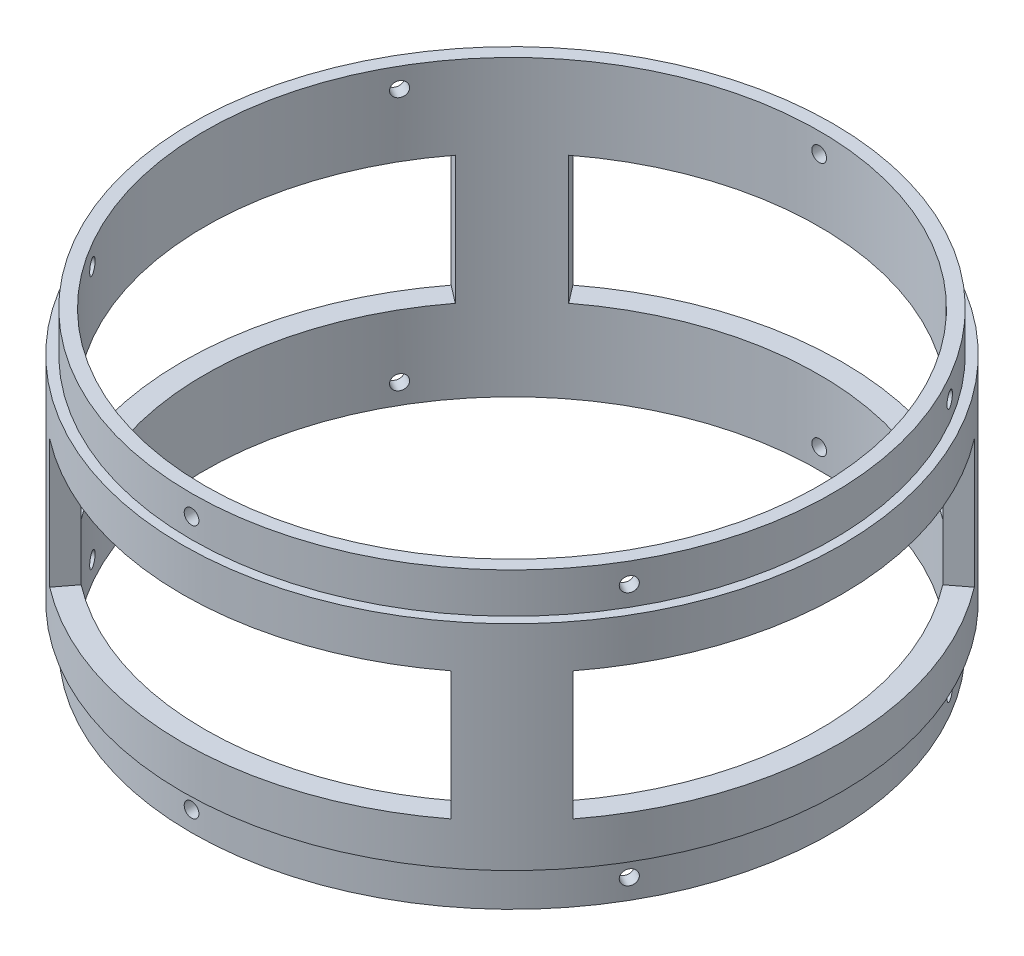
SolidWorks part; units mm, degrees
ref_plane "Front Plane" through (0, 0, 0) normal (0, 0, 1) x (1, 0, 0)
ref_plane "Top Plane" through (0, 0, 0) normal (0, 1, 0) x (1, 0, 0)
ref_plane "Right Plane" through (0, 0, 0) normal (1, 0, 0) x (0, 0, -1)
sketch "Sketch1" plane through (0, 0, 0) normal (0, 1, 0) x (1, 0, 0)
  line L0 (0, 0) -> (-47.7019, 62.1664)
  line L1 (0, 0) -> (47.7019, 62.1664)
  line L2 (0, 0) -> (0, 72.1431) construction
  circle A0 centre (0, 0) radius 78.359
  circle A1 centre (0, 0) radius 73.025
  circle A2 centre (0, 0) radius 76.1746
  dimension "D1" = 156.718
  dimension "D2" = 146.05
  dimension "D3" = 152.3492
  dimension "D4" = 75
extrude "Boss-Extrude1" add sketch "Sketch1" along normal blind 50.8 contours L2 A2 L1 A0 | L2 A1 L1 A2 | L2 A2 L1 A1 | L2 A0 L1 A2 | A2 L2 A1 L0 | A0 L2 A2 L0 | A2 L2 A0 L0 | A1 L2 A2 L0 region at (-33.2032, 0, 67.3294) region at (-44.6636, 0, -59.7594) region at (-34.6222, 0, 70.2068) region at (-46.2669, 0, -61.8908)
ref_plane "Plane1" through (0, 25.4, 0) normal (0, 1, 0) x (1, 0, 0)
extrude "Boss-Extrude2" add sketch "Sketch1<3>" along normal blind 9.525 from surface contours A2 L2 A1 L0 | L2 A2 L1 A1 | L2 A1 L1 A2 | A1 L2 A2 L0 region at (-33.2032, 0, 67.3294) region at (-44.6636, 0, -59.7594) starting at face at (0, 50.8, 73.025)
sketch "Sketch1<3>" plane through (0, 0, 0) normal (0, 1, 0) x (1, 0, 0) same geometry as "Sketch1"
extrude "Boss-Extrude3" add sketch "Sketch1<4>" against normal blind 9.525 contours A2 L2 A1 L0 | A1 L2 A2 L0 | L2 A1 L1 A2 | L2 A2 L1 A1 region at (-33.2032, 0, 67.3294) region at (-44.6636, 0, -59.7594)
sketch "Sketch1<4>" plane through (0, 0, 0) normal (0, 1, 0) x (1, 0, 0) same geometry as "Sketch1"
ref_plane "Plane2" through (0, 0, -76.1746) normal (0, 0, -1) x (-1, 0, 0)
ref_axis "Axis1" through (0, 0, 0) along (0, 1, 0)
sketch "Sketch3" plane through (0, 0, -76.1746) normal (0, 0, -1) x (-1, 0, 0)
  line L0 (76.1746, 0) -> (-76.1746, 0) construction
  line L1 (-76.1746, -9.525) -> (76.1746, -9.525) construction
  line L2 (76.1746, 50.8) -> (-76.1746, 50.8) construction
  line L3 (76.1746, 60.325) -> (-76.1746, 60.325) construction
  line L4 (76.1746, 0) -> (-76.1746, 0)
  line L5 (-76.1746, -9.525) -> (76.1746, -9.525)
  line L6 (76.1746, 50.8) -> (-76.1746, 50.8)
  line L7 (76.1746, 60.325) -> (-76.1746, 60.325)
  line L8 (0, 60.325) -> (0, 50.8)
  line L9 (0, 0) -> (0, -9.525)
  circle A0 centre (0, 55.5625) radius 1.75
  circle A1 centre (0, -4.7625) radius 1.75
  point P12 (0, 55.5625)
  point P13 (0, -4.7625)
  point P14 (-77.5445, 179.1871)
  dimension "D1" = 3.5
extrude "Cut-Extrude2" cut sketch "Sketch3" against normal up to next contours L8 A0 | L8 A0 | L9 A1 | L9 A1 region at (-0.7427, 55.5625, -76.1746) region at (0.7427, 55.5625, -76.1746) region at (-0.7427, -4.7625, -76.1746) region at (0.7427, -4.7625, -76.1746)
extrude "Cut-Extrude3" cut sketch "Sketch1<7>" against normal blind 15.24 and the other way blind 15.24 from surface contours L2 A1 L1 A2 | A1 L2 A2 L0 | A2 L2 A0 L0 | L2 A2 L1 A0 region at (-44.6636, 0, -59.7594) region at (-46.2669, 0, -61.8908) starting at plane "Plane1"
sketch "Sketch1<7>" plane through (0, 0, 0) normal (0, 1, 0) x (1, 0, 0) same geometry as "Sketch1"
pattern_circular "CirPattern2" count 4 over 360 about axis through (0, 0, 0) along (0, 1, 0) of "Cut-Extrude3"
pattern_circular "CirPattern3" count 6 over 360 about axis through (0, 0, 0) along (0, 1, 0) of "Cut-Extrude2"
equation "\"AB_Coupler_OD_Length\"= 2in"
equation "\"AB_Coupling_Section_Length\"= 0.375in"
equation "\"AB_Coupler_Length\"= \"AB_Coupler_OD_Length\" + \"AB_Coupling_Section_Length\" * 2"
equation "\"D1@Boss-Extrude2\"=\"AB_Coupling_Section_Length\""
equation "\"D1@Boss-Extrude3\"=\"AB_Coupling_Section_Length\""
equation "\"D1@Boss-Extrude1\" = \"AB_Coupler_OD_Length\""
equation "\"Cutout_Angle\" = 75"
equation "\"AB_Coupler_Num_Screws\"= 6"
equation "\"Num_Cutouts\" = 4"
equation "\"D4@Sketch1\"=\"Cutout_Angle\""
equation "\"D1@CirPattern2\"=\"Num_Cutouts\""
equation "\"D1@CirPattern3\"=\"AB_Coupler_Num_Screws\""
equation "\"AB_Coupler_OD\"= 6.17in"
equation "\"AB_Coupler_ID\"= 5.75in"
equation "\"AB_Coupler_Surface_Diameter\"= 5.998in"
equation "\"D3@Sketch1\"=\"AB_Coupler_Surface_Diameter\""
equation "\"D2@Sketch1\"=\"AB_Coupler_ID\""
equation "\"D1@Sketch1\"=\"AB_Coupler_OD\""
equation "\"AB_Coupling_Screw_Diameter\"= 0.1065in"
equation "\"Aft_Section_Length\"= 40in"
equation "\"Aft_Lower_Length\"= 20in"
equation "\"Aft_Upper_Length\"= \"Aft_Section_Length\" - \"Aft_Lower_Length\" - \"AB_Coupler_OD_Length\""
